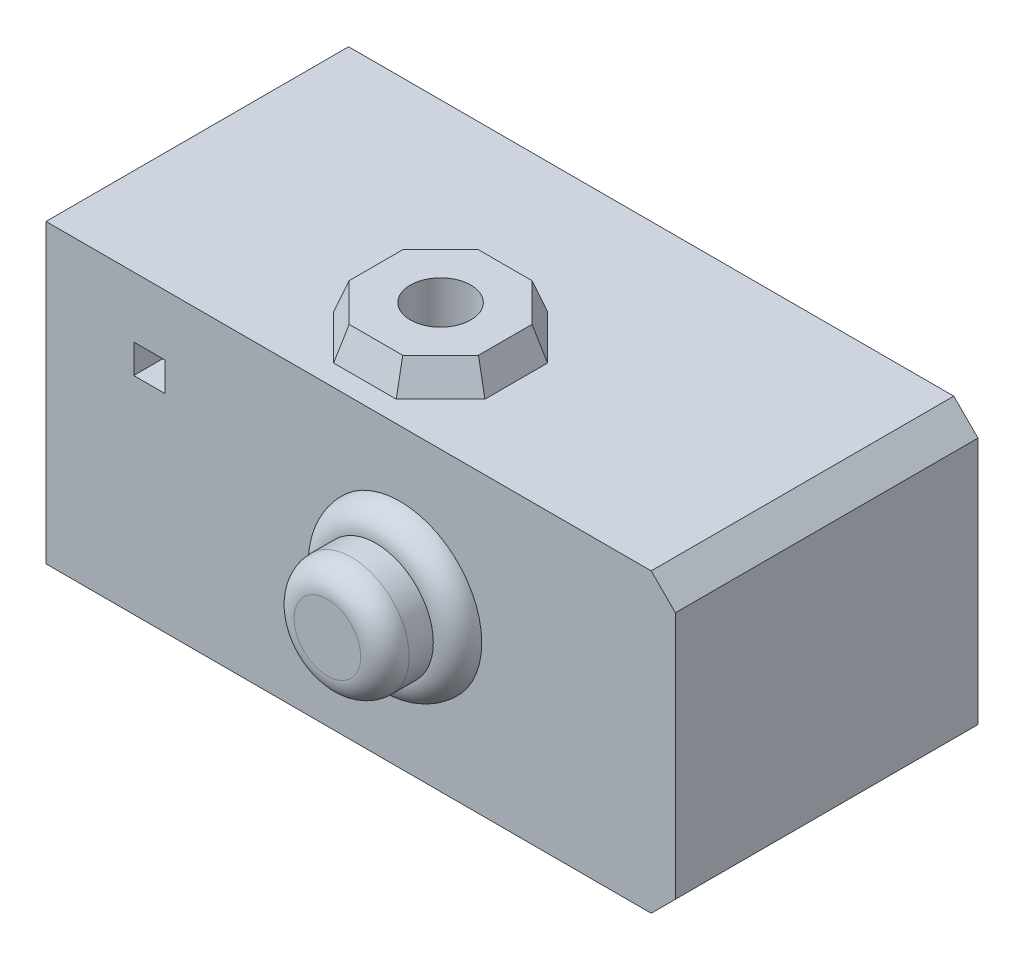
SolidWorks part; units mm, degrees
ref_plane "Front Plane" through (0, 0, 0) normal (0, 0, 1) x (1, 0, 0)
ref_plane "Top Plane" through (0, 0, 0) normal (0, 1, 0) x (1, 0, 0)
ref_plane "Right Plane" through (0, 0, 0) normal (1, 0, 0) x (0, 0, -1)
sketch "Sketch1" plane through (0, 0, 0) normal (0, 0, 1) x (1, 0, 0)
  line L1 (0, 0) -> (53, 0)
  line L2 (0, 0) -> (0, 24.5)
  line L3 (0, 24.5) -> (53, 24.5)
  line L4 (53, 0) -> (53, 24.5)
  line L5 (0, 0) -> (53, 24.5) construction
  line L6 (0, 24.5) -> (53, 0) construction
  point P4 (26.5, 12.25)
  dimension "D1" = 24.5
  dimension "D2" = 53
extrude "Boss-Extrude1" add sketch "Sketch1" along normal blind 25
sketch "Sketch2" plane through (0, 24.5, 0) normal (0, 1, 0) x (1, 0, 0)
  line L0 (53, -25) -> (0, -25) construction
  line L1 (31.85, -19.5888) -> (31.85, -14.4112)
  line L2 (31.85, -14.4112) -> (28.1888, -10.75)
  line L3 (28.1888, -10.75) -> (23.0112, -10.75)
  line L4 (23.0112, -10.75) -> (19.35, -14.4112)
  line L5 (19.35, -14.4112) -> (19.35, -19.5888)
  line L6 (19.35, -19.5888) -> (23.0112, -23.25)
  line L7 (23.0112, -23.25) -> (28.1888, -23.25)
  line L8 (28.1888, -23.25) -> (31.85, -19.5888)
  line L17 (0, -25) -> (0, 0) construction
  circle A1 centre (25.6, -17) radius 6.25 construction
  dimension "D1" = 25.6
  dimension "D2" = 8
  dimension "D3" = 12.5
extrude "Boss-Extrude2" add sketch "Sketch2" along normal blind 2.5 draft 20
sketch "Sketch3" plane through (0, 27, 0) normal (0, 1, 0) x (1, 0, 0)
  line L0 (30.9401, -17) -> (25.6, -17) construction
  line L1 (30.9401, -19.2119) -> (30.9401, -14.7881) construction
  line L2 (25.6, -22.3401) -> (25.6, -17) construction
  line L3 (23.3881, -22.3401) -> (27.8119, -22.3401) construction
  circle A0 centre (25.6, -17) radius 2.5
  point P3 (0, 0)
  dimension "D1" = 5
extrude "Cut-Extrude1" cut sketch "Sketch3" against normal through all
sketch "Sketch4" plane through (0, 0, 0) normal (-1, 0, 0) x (0, 0, 1)
  line L0 (0, 24.5) -> (0, 0) construction
  line L1 (13.2, 16.5) -> (16.86, 16.5)
  line L2 (13.2, 16.5) -> (13.2, 7.5)
  line L3 (13.2, 7.5) -> (16.86, 7.5)
  line L4 (16.86, 16.5) -> (16.86, 7.5)
  line L5 (13.2, 16.5) -> (16.86, 7.5) construction
  line L6 (13.2, 7.5) -> (16.86, 16.5) construction
  line L7 (25, 24.5) -> (0, 24.5) construction
  point P4 (15.03, 12)
  dimension "D1" = 9
  dimension "D2" = 3.66
  dimension "D3" = 13.2
  dimension "D4" = 8
extrude "Cut-Extrude2" cut sketch "Sketch4" against normal blind 5
sketch "Sketch5" plane through (5, 0, 0) normal (-1, 0, 0) x (0, 0, 1)
  line L0 (16.86, 16.5) -> (13.2, 16.5) construction
  line L1 (15.25, 15.25) -> (15.75, 15.25)
  line L2 (15.25, 15.25) -> (15.25, 14.75)
  line L3 (15.25, 14.75) -> (15.75, 14.75)
  line L4 (15.75, 15.25) -> (15.75, 14.75)
  line L5 (15.25, 15.25) -> (15.75, 14.75) construction
  line L6 (15.25, 14.75) -> (15.75, 15.25) construction
  line L8 (0, 24.5) -> (0, 0) construction
  point P4 (15.5, 15)
  point P11 (8.1627, 12.8171)
  point P12 (0, 12.1526)
  dimension "D1" = 0.5
  dimension "D2" = 0.5
  dimension "D3" = 1.5
  dimension "D4" = 15.5
extrude "Boss-Extrude3" add sketch "Sketch5" along normal blind 5
fillet "Fillet1" radius 0.1 12 edges at (5, 15, 15.25) (2.5, 14.75, 15.25) (5, 14.75, 15.5) (2.5, 14.75, 15.75) (5, 15, 15.75) (2.5, 15.25, 15.75) (2.5, 15.25, 15.25) (5, 15.25, 15.5) (0, 15.25, 15.5) (0, 15, 15.75) (0, 14.75, 15.5) (0, 15, 15.25)
pattern_linear "LPattern1" count 4 spacing 2 along (0, -1, 0) of "Boss-Extrude3", "Fillet1"
sketch "Sketch6" plane through (0, 0, 0) normal (0, 0, -1) x (-1, 0, 0)
  line L0 (0, 24.5) -> (0, 0) construction
  line L1 (-53, 24.5) -> (0, 24.5) construction
  circle A0 centre (-39, 19) radius 1.25
  circle A1 centre (-39, 6.5) radius 1.25
  circle A2 centre (-14, 19) radius 1.25
  dimension "D1" = 2.5
  dimension "D3" = 5.5
  dimension "D4" = 5.5
  dimension "D5" = 39
  dimension "D6" = 39
  dimension "D7" = 18
  dimension "D2" = 14
extrude "Cut-Extrude3" cut sketch "Sketch6" against normal blind 5
sketch "Sketch7" plane through (0, 0, 25) normal (0, 0, 1) x (1, 0, 0)
  line L0 (0, 24.5) -> (0, 0) construction
  line L1 (8.25, 19.5) -> (10.85, 19.5)
  line L2 (8.25, 19.5) -> (8.25, 17.1)
  line L3 (8.25, 17.1) -> (10.85, 17.1)
  line L4 (10.85, 19.5) -> (10.85, 17.1)
  line L5 (8.25, 19.5) -> (10.85, 17.1) construction
  line L6 (8.25, 17.1) -> (10.85, 19.5) construction
  line L7 (53, 24.5) -> (0, 24.5) construction
  point P4 (9.55, 18.3)
  dimension "D1" = 2.4
  dimension "D2" = 2.6
  dimension "D3" = 8.25
  dimension "D4" = 5
extrude "Cut-Extrude4" cut sketch "Sketch7" against normal blind 2.5
sketch "Sketch8" plane through (0, 0, 25) normal (0, 0, 1) x (1, 0, 0)
  line L0 (37, 12.35) -> (37, 22.2353) construction
  line L1 (53, 24.5) -> (0, 24.5) construction
  line L2 (30.25, 19.1) -> (40.3302, 19.1) construction
  line L3 (0, 24.5) -> (0, 0) construction
  circle A0 centre (30.25, 12.35) radius 6.75
  dimension "D4" = 13.5
  dimension "D1" = 5.4
  dimension "D3" = 37
extrude "Boss-Extrude4" add sketch "Sketch8" along normal blind 2
fillet "Fillet2" radius 2 1 edges at (37, 12.35, 27)
sketch "Sketch9" plane through (0, 0, 27) normal (0, 0, 1) x (1, 0, 0)
  circle A0 centre (30.25, 12.35) radius 4.75
extrude "Boss-Extrude5" add sketch "Sketch9" along normal blind 4
fillet "Fillet3" radius 2 1 edges at (35, 12.35, 31)
chamfer "Chamfer1" distance 1 angle 45 3 edges at (0, 0, 12.5) (0, 12.25, 25) (0, 24.5, 12.5)
chamfer "Chamfer2" distance 2 angle 45 2 edges at (53, 24.5, 12.5) (53, 0, 12.5)
